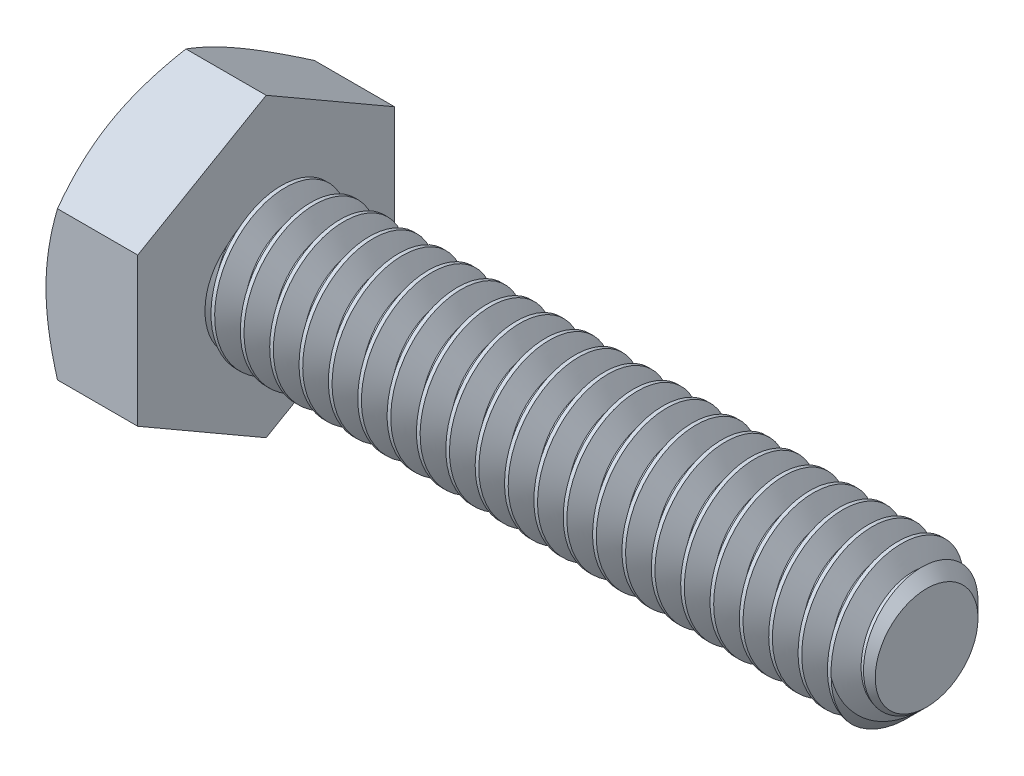
SolidWorks part; units mm, degrees
ref_plane "Front Plane" through (0, 0, 0) normal (0, 0, 1) x (1, 0, 0)
ref_plane "Top Plane" through (0, 0, 0) normal (0, 1, 0) x (1, 0, 0)
ref_plane "Right Plane" through (0, 0, 0) normal (1, 0, 0) x (0, 0, -1)
sketch "Sketch1" plane through (0, 0, 0) normal (0, 0, 1) x (1, 0, 0)
  line L0 (-16.2719, 0) -> (16.2719, 0) construction
  line L1 (16.2719, 3.175) -> (16.2719, -3.175) construction
  line L2 (-12.3031, 5.5562) -> (-12.3031, -5.5562) construction
  line L3 (-16.2719, 5.5562) -> (-16.2719, -5.5562) construction
  point P9 (-12.3031, 0)
  point P10 (11.8269, -3.175)
  dimension "Screw Dia" = 6.35
  dimension "Hex" = 11.1125
  dimension "Head Ht" = 3.9688
  dimension "Screw Lenght" = 28.575
  dimension "D1" = 4.445
ref_plane "Plane2" through (16.2719, 0, 0) normal (1, 0, 0) x (0, 0, -1)
sketch "Sketch5" plane through (16.2719, 0, 0) normal (1, 0, 0) x (0, 0, -1)
  circle A0 centre (0, 0) radius 3.175
extrude "Boss-Extrude3" add sketch "Sketch5" against normal up to vertex (28.575 mm away) up to point (-12.3031, 0, 0)
sketch "Sketch9" plane through (16.2719, 0, 0) normal (1, 0, 0) x (0, 0, -1)
  circle A1 centre (0, 0) radius 3.175
  circle A2 centre (0, 0) radius 3.175
  dimension "D1" = 0
curve "Helix/Spiral1" pitch 1.27 height 29.845 turns 23.5 parameters "Pitch"=1.27
chamfer "Chamfer1" distance 0.9525 angle 45 1 edges at (16.2719, 0, -3.175)
sketch "Sketch10" plane through (0, 0, 0) normal (0, 0, 1) x (1, 0, 0)
  line L0 (16.2719, 3.175) -> (16.7481, 2.3501)
  line L1 (16.7481, 2.3501) -> (16.9069, 2.3501)
  line L2 (16.9069, 2.3501) -> (17.3831, 3.175)
  line L3 (16.2719, 3.175) -> (17.3831, 3.175)
  line L4 (16.8275, 3.175) -> (16.8275, 2.3501) construction
  line L5 (16.51, 2.7626) -> (17.145, 2.7626) construction
  dimension "D1" = 60
  dimension "D2" = 0.1588
  dimension "D3" = 0.635
sweep "Cut-Sweep1" cut profiles "Sketch10" path "Helix/Spiral1"
sketch "Sketch6" plane through (-12.3031, 0, 0) normal (-1, 0, 0) x (0, 0, 1)
  line L0 (0, 5.5562) -> (0, -5.5562) construction
  line L1 (5.5562, 3.2079) -> (0, 6.4158)
  line L2 (0, 6.4158) -> (-5.5562, 3.2079)
  line L3 (-5.5562, 3.2079) -> (-5.5562, -3.2079)
  line L4 (-5.5562, -3.2079) -> (0, -6.4158)
  line L5 (0, -6.4158) -> (5.5563, -3.2079)
  line L6 (5.5563, -3.2079) -> (5.5562, 3.2079)
  circle A0 centre (0, 0) radius 5.5562 construction
extrude "Boss-Extrude4" add sketch "Sketch6" along normal up to vertex (3.9688 mm away) up to point (-16.2719, -5.5562, 0)
sketch "Sketch7" plane through (-16.2719, 0, 0) normal (-1, 0, 0) x (0, 0, 1)
  circle A0 centre (0, 0) radius 5.5562 construction
  circle A1 centre (0, 0) radius 5.5562
sketch "Sketch8" plane through (-16.2719, 0, 0) normal (-1, 0, 0) x (0, 0, 1)
  circle A0 centre (0, 0) radius 5.5562 construction
  circle A1 centre (0, 0) radius 5.5562
extrude "Cut-Extrude3" cut sketch "Sketch8" against normal through all draft 60 flip side to cut
equation "\"D2@Sketch10\" = \"Pitch@Helix/Spiral1\"*.125"
equation "\"D3@Sketch10\" = \"Pitch@Helix/Spiral1\"*.5"
equation "\"D3@Helix/Spiral1\" = \"Screw Lenght@Sketch1\"+\"Pitch@Helix/Spiral1\""
equation "\"D1@Chamfer1\" = \"Pitch@Helix/Spiral1\"*.75"
equation "\"D1@Sketch1\" = \"Pitch@Helix/Spiral1\"*3.5"
